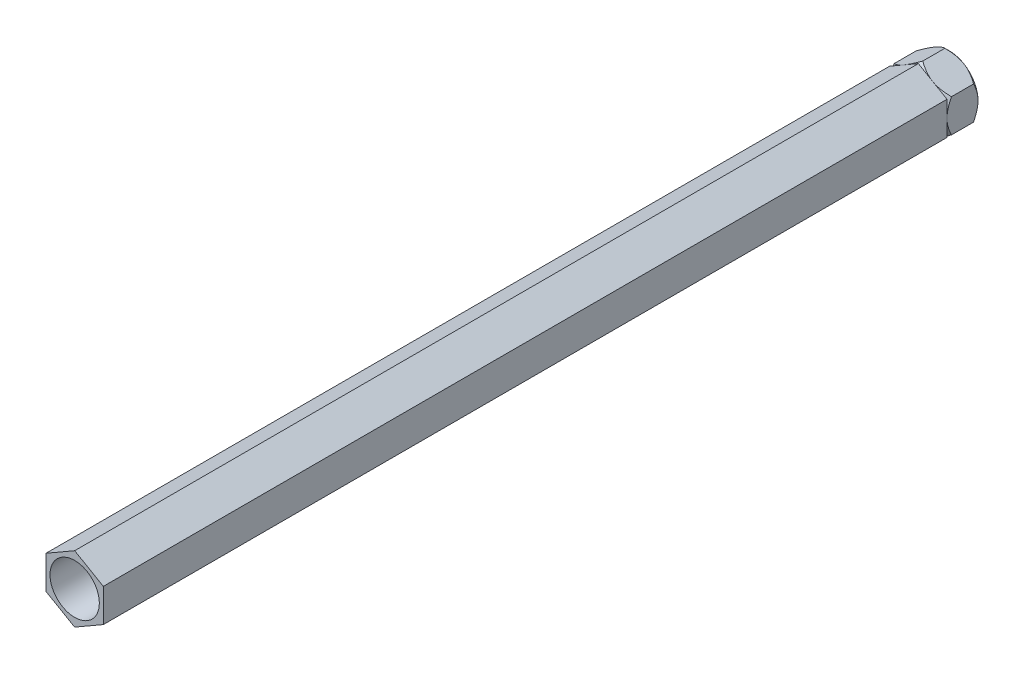
SolidWorks part; units mm, degrees
material "Alloy Steel"
ref_plane "Front" through (0, 0, 0) normal (0, 0, 1) x (1, 0, 0)
ref_plane "Top" through (0, 0, 0) normal (0, 1, 0) x (1, 0, 0)
ref_plane "Right" through (0, 0, 0) normal (1, 0, 0) x (0, 0, -1)
sketch "Sketch1" plane through (0, 0, 0) normal (0, 0, 1) x (1, 0, 0)
  line L1 (0, -12.8172) -> (11.1, -6.4086)
  line L2 (11.1, -6.4086) -> (11.1, 6.4086)
  line L3 (11.1, 6.4086) -> (0, 12.8172)
  line L4 (0, 12.8172) -> (-11.1, 6.4086)
  line L5 (-11.1, 6.4086) -> (-11.1, -6.4086)
  line L6 (-11.1, -6.4086) -> (0, -12.8172)
  circle A0 centre (0, 0) radius 11.1 construction
  circle A1 centre (0, 0) radius 6
  dimension "Width" = 22.2
  dimension "ThreadDia" = 12
extrude "Boss-Extrude1" add sketch "Sketch1" along normal mid plane 12
sketch "Sketch2" plane through (0, 0, 6) normal (0, 0, 1) x (1, 0, 0)
  circle A0 centre (0, 0) radius 6 construction
  circle A1 centre (0, 0) radius 6
curve "Helix/Spiral1" pitch 3 height 15 radius 6 centre (0, 0, 6) axis (0, 0, -1) start towards (0, 1, 0) parameters "Pitch"=3
sketch "Sketch3" plane through (0, 0, 0) normal (1, 0, 0) x (0, 0, -1)
  line L0 (-6, 6) -> (-6.3879, 4.5001)
  line L1 (-6, 6.4086) -> (-6, -6.4086) construction
  line L2 (-6, 6) -> (-6, -6) construction
  line L3 (-6.3879, 4.5001) -> (-7.5, 4.5001)
  line L4 (-7.5, 4.5001) -> (-7.8879, 6)
  line L5 (-7.8879, 6) -> (-6, 6)
  line L6 (-7.6939, 5.2501) -> (-6.1939, 5.2501) construction
  line L7 (-6.9439, 5.2501) -> (-6.9439, 4.5001) construction
  spline S0 degree 3 poles (-6, 6) (-5.9379, 6) (-5.8123, 5.6876) (-5.625, 4.3531) (-5.4375, 2.3559) (-5.25, 0) (-5.0625, -2.3559) (-4.875, -4.3531) (-4.6875, -5.6876) (-4.5, -6.1562) (-4.3125, -5.6876) (-4.125, -4.3531) (-3.9375, -2.3559) (-3.75, 0) (-3.5625, 2.3559) (-3.375, 4.3531) (-3.1875, 5.6876) (-3, 6.1562) (-2.8125, 5.6876) (-2.625, 4.3531) (-2.4375, 2.3559) (-2.25, 0) (-2.0625, -2.3559) (-1.875, -4.3531) (-1.6875, -5.6876) (-1.5, -6.1562) (-1.3125, -5.6876) (-1.125, -4.3531) (-0.9375, -2.3559) (-0.75, 0) (-0.5625, 2.3559) (-0.375, 4.3531) (-0.1875, 5.6876) (0, 6.1562) (0.1875, 5.6876) (0.375, 4.3531) (0.5625, 2.3559) (0.75, 0) (0.9375, -2.3559) (1.125, -4.3531) (1.3125, -5.6876) (1.5, -6.1562) (1.6875, -5.6876) (1.875, -4.3531) (2.0625, -2.3559) (2.25, 0) (2.4375, 2.3559) (2.625, 4.3531) (2.8125, 5.6876) (3, 6.1562) (3.1875, 5.6876) (3.375, 4.3531) (3.5625, 2.3559) (3.75, 0) (3.9375, -2.3559) (4.125, -4.3531) (4.3125, -5.6876) (4.5, -6.1562) (4.6875, -5.6876) (4.875, -4.3531) (5.0625, -2.3559) (5.25, 0) (5.4375, 2.3559) (5.625, 4.3531) (5.8125, 5.6876) (6, 6.1562) (6.1875, 5.6876) (6.375, 4.3531) (6.5625, 2.3559) (6.75, 0) (6.9375, -2.3559) (7.125, -4.3531) (7.3125, -5.6876) (7.5, -6.1562) (7.6875, -5.6876) (7.875, -4.3531) (8.0625, -2.3559) (8.25, 0) (8.4375, 2.3559) (8.625, 4.3531) (8.8123, 5.6876) (8.9379, 6) (9, 6) knots 0 0 0 0 0.0125 0.025 0.0375 0.05 0.0625 0.075 0.0875 0.1 0.1125 0.125 0.1375 0.15 0.1625 0.175 0.1875 0.2 0.2125 0.225 0.2375 0.25 0.2625 0.275 0.2875 0.3 0.3125 0.325 0.3375 0.35 0.3625 0.375 0.3875 0.4 0.4125 0.425 0.4375 0.45 0.4625 0.475 0.4875 0.5 0.5125 0.525 0.5375 0.55 0.5625 0.575 0.5875 0.6 0.6125 0.625 0.6375 0.65 0.6625 0.675 0.6875 0.7 0.7125 0.725 0.7375 0.75 0.7625 0.775 0.7875 0.8 0.8125 0.825 0.8375 0.85 0.8625 0.875 0.8875 0.9 0.9125 0.925 0.9375 0.95 0.9625 0.975 0.9875 1 1 1 1 construction
  dimension "D1" = 29
  dimension "D2" = 1.1121
  dimension "D3" = 1.5
sketch "Sketch4" plane through (0, 0, 6) normal (0, 0, 1) x (1, 0, 0)
  circle A0 centre (0, 0) radius 6.381
  circle A1 centre (0, 0) radius 6 construction
  dimension "D1" = 0.381
sketch "Sketch5" plane through (0, 0, -6) normal (0, 0, -1) x (-1, 0, 0)
  circle A1 centre (0, 0) radius 6.381
  circle A2 centre (0, 0) radius 6.381
  dimension "D1" = 0
sweep "Sweep1" add profiles "Sketch3" path "Helix/Spiral1"
extrude "Cut-Extrude1" cut sketch "Sketch4" along normal through all
extrude "Cut-Extrude2" cut sketch "Sketch5" along normal through all
extrude "Cut-Extrude3" cut sketch "Sketch4<2>" against normal through all draft 45
sketch "Sketch4<2>" plane through (0, 0, 6) normal (0, 0, 1) x (1, 0, 0) same geometry as "Sketch4"
extrude "Cut-Extrude4" cut sketch "Sketch5<2>" against normal through all draft 45
sketch "Sketch5<2>" plane through (0, 0, -6) normal (0, 0, -1) x (-1, 0, 0) same geometry as "Sketch5"
sketch "Sketch6" plane through (0, 0, 6) normal (0, 0, 1) x (1, 0, 0)
  line L0 (-11.1, 0) -> (0, 0) construction
  line L2 (-11.1, 6.4086) -> (-11.1, -6.4086) construction
  circle A0 centre (0, 0) radius 11.1
extrude "Cut-Extrude5" cut sketch "Sketch6" against normal through all draft 45 flip side to cut
sketch "Sketch7" plane through (0, 0, -6) normal (0, 0, -1) x (-1, 0, 0)
  circle A1 centre (0, 0) radius 11.1
  circle A2 centre (0, 0) radius 11.1
  dimension "D1" = 0
extrude "Cut-Extrude6" cut sketch "Sketch7" against normal through all draft 45 flip side to cut
sketch "Sketch8" plane through (0, 0, 6) normal (0, 0, 1) x (1, 0, 0)
  line L1 (0, -12.8172) -> (11.1, -6.4086)
  line L2 (11.1, -6.4086) -> (11.1, 6.4086)
  line L3 (11.1, 6.4086) -> (0, 12.8172)
  line L4 (0, 12.8172) -> (-11.1, 6.4086)
  line L5 (-11.1, 6.4086) -> (-11.1, -6.4086)
  line L6 (-11.1, -6.4086) -> (0, -12.8172)
  circle A0 centre (0, 0) radius 11.1 construction
  circle A1 centre (0, 0) radius 9.5498
extrude "Boss-Extrude2" add sketch "Sketch8" along normal blind 326.644
equation "\"D3@Helix/Spiral1\" = \"Height@Boss-Extrude1\"+\"Pitch@Helix/Spiral1\""
equation "\"D2@Sketch3\" = \"Pitch@Helix/Spiral1\"*.3707"
equation "\"D3@Sketch3\" = \"Pitch@Helix/Spiral1\"*.5"
